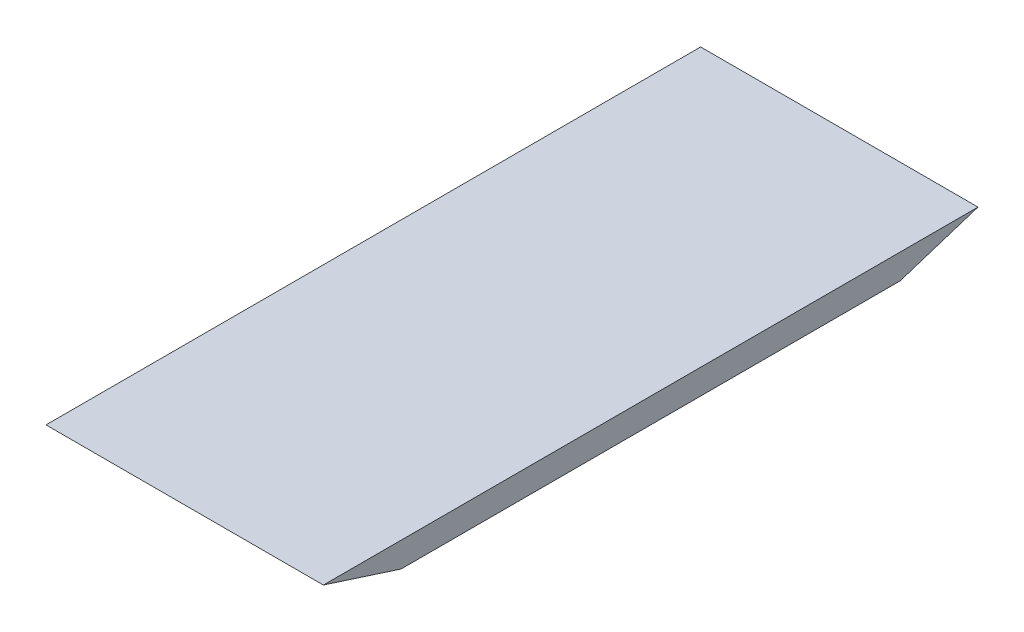
SolidWorks part; units mm, degrees
ref_plane "Front Plane" through (0, 0, 0) normal (0, 0, 1) x (1, 0, 0)
ref_plane "Top Plane" through (0, 0, 0) normal (0, 1, 0) x (1, 0, 0)
ref_plane "Right Plane" through (0, 0, 0) normal (1, 0, 0) x (0, 0, -1)
sketch "Sketch1" plane through (0, 0, 0) normal (1, 0, 0) x (0, 0, -1)
  line L0 (0, 0) -> (236, 0)
  line L1 (236, 0) -> (208, -9)
  line L2 (208, -9) -> (28, -9)
  line L3 (28, -9) -> (0, 0)
  point P3 (118, 0)
  dimension "D1" = 180
  dimension "D2" = 28
  dimension "D3" = 28
  dimension "D4" = 9
extrude "Boss-Extrude1" add sketch "Sketch1" along normal blind 100
